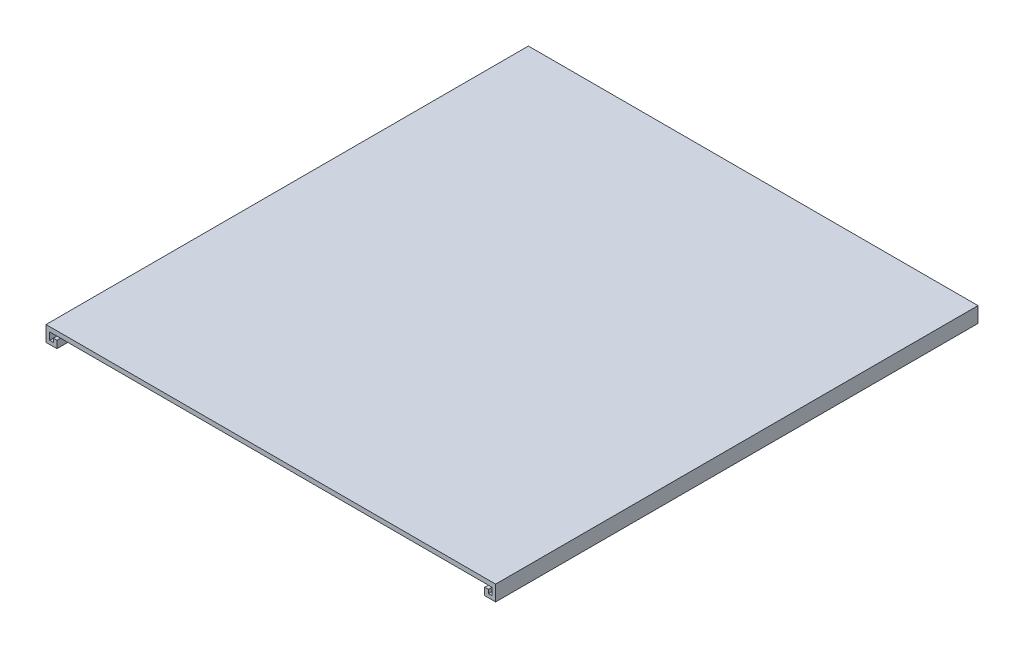
SolidWorks part; units mm, degrees
ref_plane "Front Plane" through (0, 0, 0) normal (0, 0, 1) x (1, 0, 0)
ref_plane "Top Plane" through (0, 0, 0) normal (0, 1, 0) x (1, 0, 0)
ref_plane "Right Plane" through (0, 0, 0) normal (1, 0, 0) x (0, 0, -1)
sketch "Sketch2" plane through (0, 0, 0) normal (0, 1, 0) x (1, 0, 0)
  line L1 (-121.5, 132.5) -> (121.5, 132.5)
  line L2 (-121.5, 132.5) -> (-121.5, -132.5)
  line L3 (-121.5, -132.5) -> (121.5, -132.5)
  line L4 (121.5, 132.5) -> (121.5, -132.5)
  line L5 (-121.5, 132.5) -> (121.5, -132.5) construction
  line L6 (-121.5, -132.5) -> (121.5, 132.5) construction
  point P0 (0, 0)
  dimension "D1" = 243
  dimension "D2" = 265
extrude "Boss-Extrude1" add sketch "Sketch2" along normal blind 2.5 contours L1 L4 L3 L2
sketch "Sketch3" plane through (0, 0, 0) normal (0, -1, 0) x (1, 0, 0)
  line L1 (-121.5, -132.5) -> (-123.5, -132.5)
  line L2 (-121.5, -132.5) -> (-121.5, 132.5)
  line L3 (-121.5, 132.5) -> (-123.5, 132.5)
  line L4 (-123.5, -132.5) -> (-123.5, 132.5)
  line L5 (121.5, 132.5) -> (123.5, 132.5)
  line L6 (121.5, 132.5) -> (121.5, -132.5)
  line L7 (121.5, -132.5) -> (123.5, -132.5)
  line L8 (123.5, 132.5) -> (123.5, -132.5)
  dimension "D1" = 2
  dimension "D2" = 2
extrude "Boss-Extrude2" add sketch "Sketch3" along normal blind 4 and the other way blind 2.5 contours L6 L7 L8 L5
sketch "Sketch4" plane through (0, 0, 0) normal (0, -1, 0) x (1, 0, 0)
  line L1 (-121.5, 132.5) -> (-123.5, 132.5)
  line L2 (-121.5, 132.5) -> (-121.5, -132.5)
  line L3 (-121.5, -132.5) -> (-123.5, -132.5)
  line L4 (-123.5, 132.5) -> (-123.5, -132.5)
  dimension "D1" = 2
extrude "Boss-Extrude3" add sketch "Sketch4" along normal blind 4 and the other way blind 2.5 contours L4 L3 L2 L1
sketch "Sketch5" plane through (-121.5, 0, 0) normal (1, 0, 0) x (0, 0, -1)
  line L1 (-132.5, -4) -> (132.5, -4)
  line L2 (-132.5, -4) -> (-132.5, -6)
  line L3 (-132.5, -6) -> (132.5, -6)
  line L4 (132.5, -4) -> (132.5, -6)
  dimension "D1" = 2
extrude "Boss-Extrude4" add sketch "Sketch5" along normal blind 2 and the other way blind 2 contours L3 L4 L1 L2
sketch "Sketch6" plane through (121.5, 0, 0) normal (-1, 0, 0) x (0, 0, 1)
  line L1 (-132.5, -4) -> (132.5, -4)
  line L2 (-132.5, -4) -> (-132.5, -6)
  line L3 (-132.5, -6) -> (132.5, -6)
  line L4 (132.5, -4) -> (132.5, -6)
  dimension "D1" = 2
extrude "Boss-Extrude5" add sketch "Sketch6" along normal blind 2 and the other way blind 2 contours L3 L4 L1 L2
sketch "Sketch7" plane through (0, -6, 0) normal (0, -1, 0) x (1, 0, 0)
  line L0 (-121.5, -132.5) -> (121.5, -132.5) construction
  line L1 (119.5, 132.5) -> (117.5, 132.5)
  line L2 (119.5, 132.5) -> (119.5, -132.5)
  line L3 (119.5, -132.5) -> (117.5, -132.5)
  line L4 (117.5, 132.5) -> (117.5, -132.5)
  dimension "D1" = 2
extrude "Boss-Extrude7" add sketch "Sketch7" against normal blind 4 contours L4 L3 L2 L1
sketch "Sketch8" plane through (0, -6, 0) normal (0, -1, 0) x (1, 0, 0)
  line L0 (-121.5, -132.5) -> (121.5, -132.5) construction
  line L1 (-119.5, 132.5) -> (-117.5, 132.5)
  line L2 (-119.5, 132.5) -> (-119.5, -132.5)
  line L3 (-119.5, -132.5) -> (-117.5, -132.5)
  line L4 (-117.5, 132.5) -> (-117.5, -132.5)
  dimension "D1" = 2
extrude "Boss-Extrude8" add sketch "Sketch8" against normal blind 4
